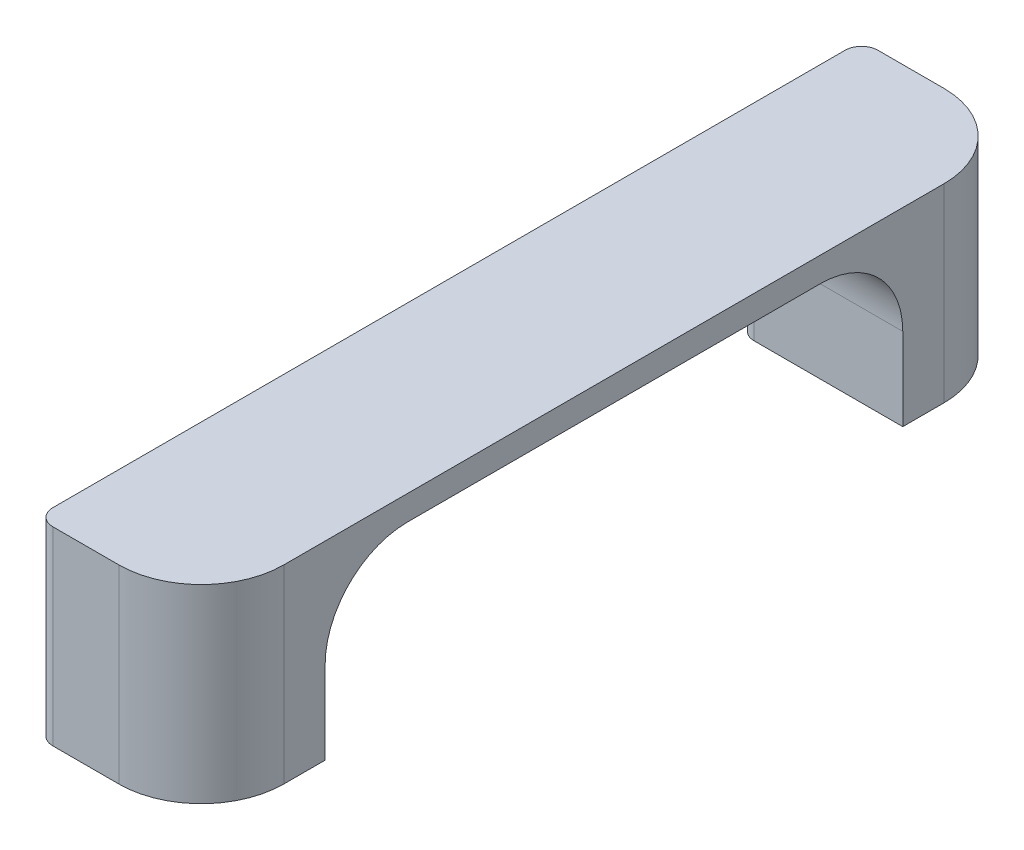
SolidWorks part; units mm, degrees
ref_plane "Alzado" through (0, 0, 0) normal (0, 0, 1) x (1, 0, 0)
ref_plane "Planta" through (0, 0, 0) normal (0, 1, 0) x (1, 0, 0)
ref_plane "Vista lateral" through (0, 0, 0) normal (1, 0, 0) x (0, 0, -1)
sketch "Croquis1" plane through (0, 0, 0) normal (0, 1, 0) x (1, 0, 0)
  line L1 (0, 0) -> (20, 0)
  line L2 (0, 0) -> (0, 90)
  line L3 (0, 90) -> (20, 90)
  line L4 (20, 0) -> (20, 90)
  dimension "D1" = 90
  dimension "D2" = 20
extrude "Saliente-Extruir1" add sketch "Croquis1" along normal blind 3
sketch "Croquis2" plane through (0, 0, 0) normal (0, -1, 0) x (1, 0, 0)
  line L0 (0, -90) -> (0, 0) construction
  line L1 (20, 0) -> (0, 0)
  line L2 (20, 0) -> (20, -10)
  line L3 (20, -10) -> (0, -10)
  line L4 (0, 0) -> (0, -10)
  line L5 (20, -90) -> (0, -90)
  line L6 (20, -90) -> (20, -80)
  line L7 (20, -80) -> (0, -80)
  line L8 (0, -90) -> (0, -80)
  line L9 (10, 0) -> (10, -90) construction
  dimension "D1" = 10
  dimension "D2" = 10
extrude "Saliente-Extruir2" add sketch "Croquis2" along normal blind 20
sketch "Croquis3" plane through (0, -20, 0) normal (0, -1, 0) x (1, 0, 0)
  line L0 (20, -5) -> (0, -5) construction
  line L1 (20, -10) -> (20, 0) construction
  line L2 (0, 0) -> (0, -10) construction
  line L8 (20, -85) -> (0, -85) construction
  line L9 (20, -90) -> (20, -80) construction
  line L10 (0, -80) -> (0, -90) construction
  circle A0 centre (12, -5) radius 2.1
  circle A1 centre (12, -85) radius 2.1
  point P6 (0, 0)
  point P7 (0, 0)
  point P8 (11.266, -5)
  point P9 (12.7804, -5)
  point P10 (0, 0)
  point P11 (10, -85)
  point P20 (0, 0)
  point P21 (14.6094, -85)
  point P22 (14.3663, -85)
  dimension "D1" = 4.2
  dimension "D2" = 4.2
  dimension "D3" = 8
extrude "Cortar-Extruir1" cut sketch "Croquis3" against normal blind 4
sketch "Croquis4" plane through (0, 3, 0) normal (0, 1, 0) x (1, 0, 0)
  line L0 (0, 0) -> (20, 0) construction
  line L1 (20, 90) -> (0, 90)
  line L2 (20, 90) -> (20, 95)
  line L3 (20, 95) -> (0, 95)
  line L4 (0, 90) -> (0, 95)
  line L5 (0, 0) -> (20, 0)
  line L6 (0, 0) -> (0, -5)
  line L7 (0, -5) -> (20, -5)
  line L8 (20, 0) -> (20, -5)
  point P5 (19.0566, -5)
  point P12 (20, 0)
  point P15 (16.3689, -5)
  point P16 (20, 0)
  dimension "D1" = 5
  dimension "D2" = 5
extrude "Saliente-Extruir3" add sketch "Croquis4" against normal up to surface (23 mm away) up to face at (12, -20, -87.1)
fillet "Redondeo1" radius 10 2 edges at (20, -8.5, 5) (20, -8.5, -95)
fillet "Redondeo2" radius 2 4 edges at (0, -8.5, 5) (0, -10, -10) (0, -10, -80) (0, -8.5, -95)
fillet "Redondeo3" radius 10 4 edges at (0.5858, 0, -80.5858) (0.5858, 0, -9.4142) (11, 0, -80) (11, 0, -10)
